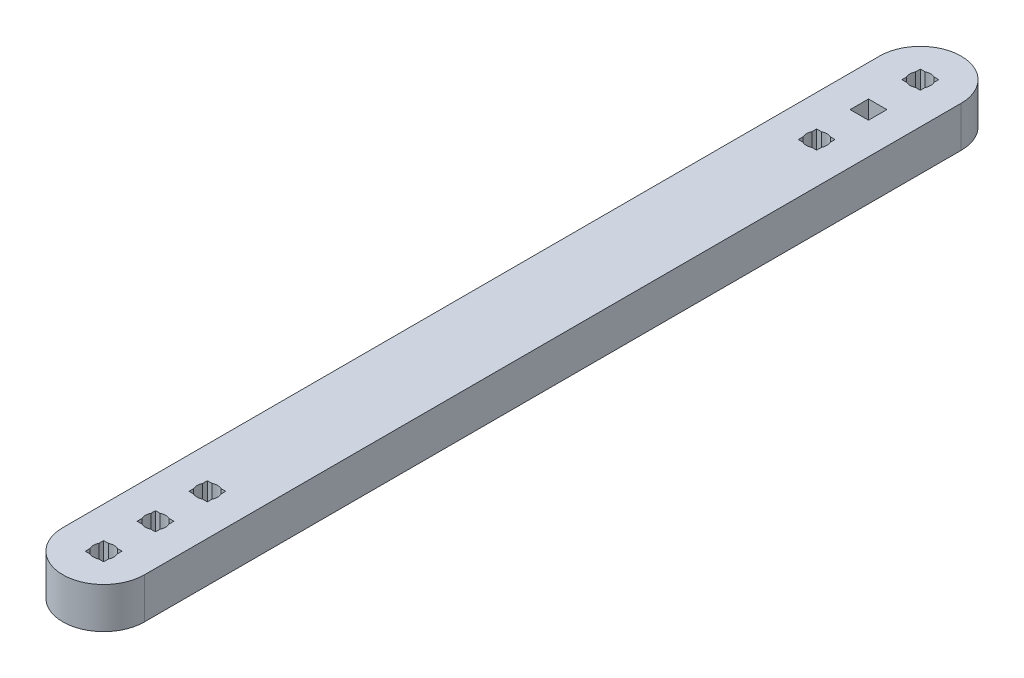
SolidWorks part; units mm, degrees
ref_plane "Front Plane" through (0, 0, 0) normal (0, 0, 1) x (1, 0, 0)
ref_plane "Top Plane" through (0, 0, 0) normal (0, 1, 0) x (1, 0, 0)
ref_plane "Right Plane" through (0, 0, 0) normal (1, 0, 0) x (0, 0, -1)
sketch "Sketch1" plane through (0, 0, 0) normal (0, 1, 0) x (1, 0, 0)
  line L0 (-10, 100) -> (10, 100) construction
  line L2 (10, -100) -> (10, 100)
  line L4 (-10, -100) -> (-10, 100)
  line L5 (10, -100) -> (-10, 100) construction
  line L6 (10, 100) -> (-10, -100) construction
  line L15 (-10, 0) -> (10, 0) construction
  circle A2 centre (0, -87.3) radius 2.5
  circle A4 centre (0, -100) radius 2.5
  circle A6 centre (0, -74.6) radius 2.5
  circle A8 centre (0, 74.6) radius 2.5
  circle A9 centre (0, 100) radius 2.5
  arc A10 (10, -100) -> (-10, -100) centre (0, -100) cw
  arc A11 (10, 100) -> (-10, 100) centre (0, 100) ccw
  point P0 (0, 0)
  dimension "D3" = 5
  dimension "D1" = 200
  dimension "D2" = 20
  dimension "D5" = 12.7
  dimension "D7" = 12.7
extrude "Boss-Extrude1" add sketch "Sketch1" along normal blind 10 contours L2 L4 A2 region at (0, 0, -0.4066)
sketch "Sketch2" plane through (0, 0, 0) normal (0, -1, 0) x (1, 0, 0)
  line L0 (10, 0) -> (-10, 0) construction
  line L5 (-2.25, -72.35) -> (2.25, -76.85) construction
  line L6 (-2.25, 102.25) -> (2.25, 102.25)
  line L11 (-2.25, 102.25) -> (-2.25, 97.75)
  line L12 (-2.25, 97.75) -> (2.25, 97.75)
  line L17 (2.25, 102.25) -> (2.25, 97.75)
  line L18 (-2.25, 102.25) -> (2.25, 97.75) construction
  line L19 (10, 100) -> (10, -100) construction
  line L20 (-10, -100) -> (-10, 100) construction
  line L21 (-2.25, 97.75) -> (2.25, 102.25) construction
  line L22 (-2.25, 89.55) -> (2.25, 89.55)
  line L23 (-2.25, 89.55) -> (-2.25, 85.05)
  line L24 (-2.25, 85.05) -> (2.25, 85.05)
  line L25 (2.25, 89.55) -> (2.25, 85.05)
  line L26 (-2.25, 89.55) -> (2.25, 85.05) construction
  line L31 (-2.25, 85.05) -> (2.25, 89.55) construction
  line L32 (-2.25, 76.85) -> (2.25, 76.85)
  line L33 (-2.25, 76.85) -> (-2.25, 72.35)
  line L34 (-2.25, 72.35) -> (2.25, 72.35)
  line L35 (2.25, 76.85) -> (2.25, 72.35)
  line L36 (-2.25, 76.85) -> (2.25, 72.35) construction
  line L37 (-2.25, 72.35) -> (2.25, 76.85) construction
  line L38 (-2.25, -76.85) -> (2.25, -72.35) construction
  line L39 (-2.25, -85.05) -> (2.25, -89.55) construction
  line L40 (-2.25, -89.55) -> (2.25, -85.05) construction
  line L41 (-2.25, -97.75) -> (2.25, -102.25) construction
  line L42 (-2.25, -102.25) -> (2.25, -97.75) construction
  line L43 (2.25, -76.85) -> (2.25, -72.35)
  line L44 (-2.25, -72.35) -> (2.25, -72.35)
  line L45 (-2.25, -76.85) -> (-2.25, -72.35)
  line L46 (-2.25, -76.85) -> (2.25, -76.85)
  line L47 (2.25, -89.55) -> (2.25, -85.05)
  line L48 (-2.25, -85.05) -> (2.25, -85.05)
  line L49 (-2.25, -89.55) -> (-2.25, -85.05)
  line L50 (-2.25, -89.55) -> (2.25, -89.55)
  line L51 (2.25, -102.25) -> (2.25, -97.75)
  line L52 (-2.25, -97.75) -> (2.25, -97.75)
  line L53 (-2.25, -102.25) -> (-2.25, -97.75)
  line L54 (-2.25, -102.25) -> (2.25, -102.25)
  point P0 (0, 100)
  point P5 (0, 87.3)
  point P10 (0, 74.6)
  point P33 (0, -74.6)
  point P34 (0, -87.3)
  point P35 (0, -100)
  dimension "D1" = 4.5
extrude "Cut-Extrude1" cut sketch "Sketch2" against normal through all
sketch "Sketch3" plane through (0, 0, 0) normal (0, -1, 0) x (1, 0, 0)
  line L0 (5, 102.51) -> (2.46, 105.05)
  line L1 (2.46, 105.05) -> (-2.46, 105.05)
  line L2 (5, 102.51) -> (5, 72.09)
  line L3 (2.46, 69.55) -> (-2.46, 69.55)
  line L4 (-5, 102.51) -> (-5, 72.09)
  line L5 (5, 105.05) -> (-5, 69.55) construction
  line L6 (5, 69.55) -> (-5, 105.05) construction
  line L7 (-2.46, 105.05) -> (-5, 102.51)
  line L8 (-2.46, 69.55) -> (-5, 72.09)
  line L9 (5, 72.09) -> (2.46, 69.55)
  line L10 (10, 0) -> (-10, 0) construction
  line L11 (10, 100) -> (10, -100) construction
  line L12 (-10, -100) -> (-10, 100) construction
  line L13 (5, -69.55) -> (-5, -105.05) construction
  line L14 (5, -105.05) -> (-5, -69.55) construction
  line L15 (5, -72.09) -> (2.46, -69.55)
  line L16 (-2.46, -69.55) -> (-5, -72.09)
  line L17 (-2.46, -105.05) -> (-5, -102.51)
  line L18 (-5, -102.51) -> (-5, -72.09)
  line L19 (2.46, -69.55) -> (-2.46, -69.55)
  line L20 (5, -102.51) -> (5, -72.09)
  line L21 (2.46, -105.05) -> (-2.46, -105.05)
  line L22 (5, -102.51) -> (2.46, -105.05)
  point P0 (0, 87.3)
  point P32 (0, -87.3)
  dimension "D1" = 10
  dimension "D2" = 35.5
extrude "Cut-Extrude2" cut sketch "Sketch3" against normal blind 5
